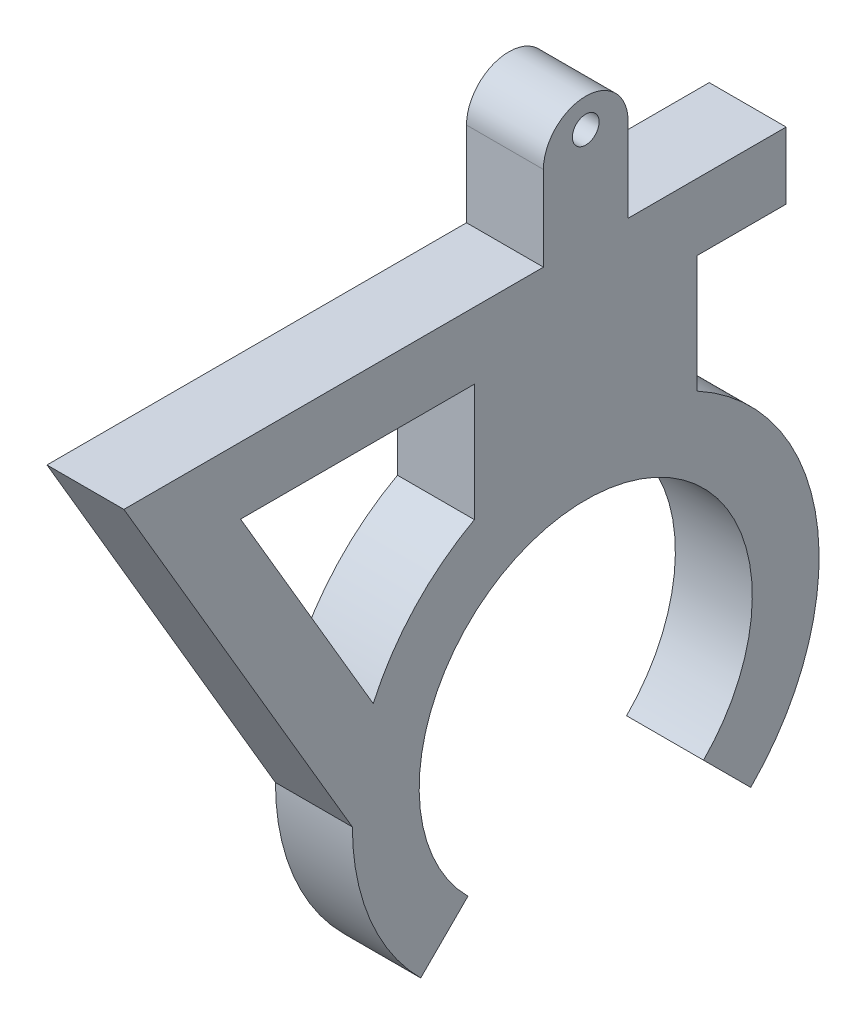
SolidWorks part; units mm, degrees
ref_plane "Front Plane" through (0, 0, 0) normal (0, 0, 1) x (1, 0, 0)
ref_plane "Top Plane" through (0, 0, 0) normal (0, 1, 0) x (1, 0, 0)
ref_plane "Right Plane" through (0, 0, 0) normal (1, 0, 0) x (0, 0, -1)
sketch "Sketch1" plane through (0, 0, 0) normal (1, 0, 0) x (0, 0, -1)
  line L0 (-2.6446, -2.6446) -> (2.6446, -2.6446) construction
  line L1 (-2.6446, -2.6446) -> (-3.7052, -3.7052)
  line L2 (3.7052, -3.7052) -> (2.6446, -2.6446)
  line L3 (0, 0) -> (0, 6.3411) construction
  line L4 (-2.5, 8.74) -> (-0.95, 8.74)
  line L5 (-2.5, 8.74) -> (-2.5, 4.6052)
  line L6 (-0.95, 10.64) -> (-0.95, 8.74)
  line L7 (2.5, 8.74) -> (2.5, 4.6052)
  line L8 (-2.5, 8.74) -> (2.5, 4.6052) construction
  line L9 (-2.5, 4.6052) -> (2.5, 8.74) construction
  line L10 (-0.95, 10.64) -> (0.95, 10.64) construction
  line L11 (0.95, 8.74) -> (2.5, 8.74)
  line L12 (0.95, 10.64) -> (0.95, 8.74)
  line L13 (-0.95, 10.64) -> (0.95, 8.74) construction
  line L14 (-0.95, 8.74) -> (0.95, 10.64) construction
  line L15 (-2.5, 8.74) -> (-10.3701, 8.74)
  line L16 (-10.3701, 8.74) -> (-5.24, 0)
  line L17 (-2.5, 7.24) -> (-7.7503, 7.24)
  line L18 (-7.7503, 7.24) -> (-4.7717, 2.1653)
  line L19 (-7.7503, 7.24) -> (-3.9464, 0.7593) construction
  line L21 (2.5, 8.74) -> (4.5, 8.74)
  line L22 (2.5, 8.74) -> (2.5, 7.24)
  line L23 (2.5, 7.24) -> (4.5, 7.24)
  line L24 (4.5, 8.74) -> (4.5, 7.24)
  arc A0 (-2.6446, -2.6446) -> (2.6446, -2.6446) centre (0, 0) cw
  arc A1 (-3.7052, -3.7052) -> (-2.5, 4.6052) centre (0, 0) cw
  arc A2 (2.5, 4.6052) -> (3.7052, -3.7052) centre (0, 0) cw
  arc A3 (-3.7052, -3.7052) -> (3.7052, -3.7052) centre (0, 0) cw construction
  arc A4 (-0.95, 10.64) -> (0.95, 10.64) centre (0, 10.64) cw
  circle A5 centre (0, 10.94) radius 0.3
  point P7 (0, 6.6726)
  point P12 (0, 3.74)
  point P16 (0, 10.64)
  point P17 (0, 9.69)
  dimension "D1" = 3.74
  dimension "D3" = 1.5
  dimension "D6" = 1.9
  dimension "D8" = 0.6
  dimension "D9" = 1.5
  dimension "D2" = 90
  dimension "D4" = 5
  dimension "D5" = 5
  dimension "D7" = 1.9
  dimension "D10" = 2
extrude "Boss-Extrude1" add sketch "Sketch1" along normal blind 1.7272 contours A4 L6 L4 L5 A1 L1 A0 L2 A2 L7 L11 L12 A5 | L16 A1 L18 L17 L5 L15 | L24 L21 L7 L23 region at (0, 3.967, 0) region at (0, 4.4295, 7.7036) region at (0, 7.99, -3.5)
